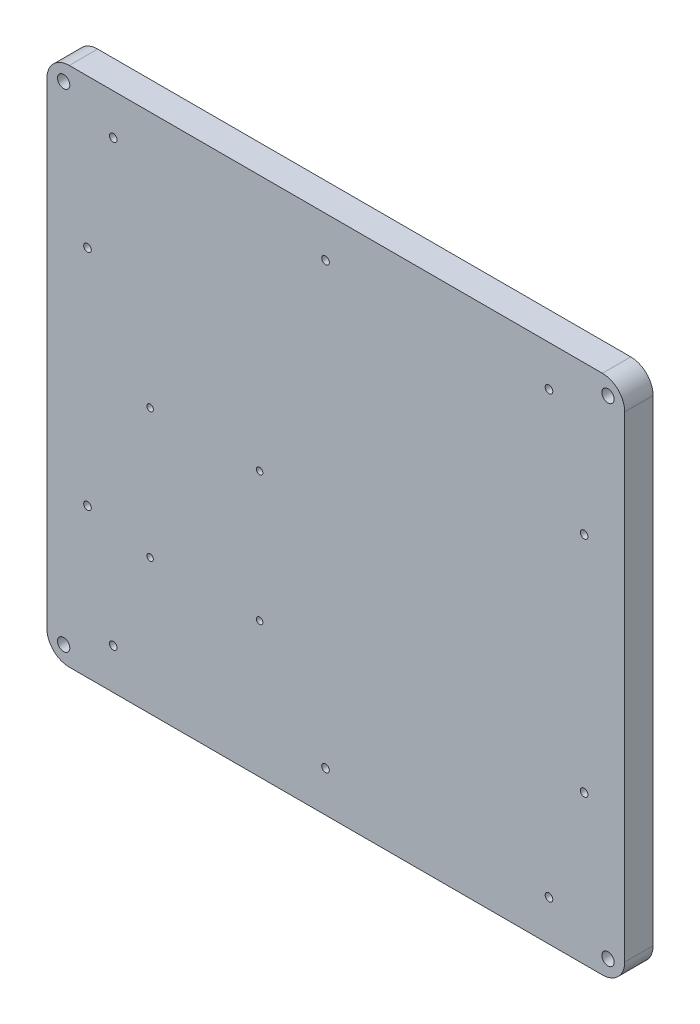
SolidWorks part; units mm, degrees
material "Aleación 6061"
ref_plane "Alzado" through (0, 0, 0) normal (0, 0, 1) x (1, 0, 0)
ref_plane "Planta" through (0, 0, 0) normal (0, 1, 0) x (1, 0, 0)
ref_plane "Vista lateral" through (0, 0, 0) normal (1, 0, 0) x (0, 0, -1)
ref_axis "Eje_J1" through (0, 0, -0.635) along (0, 0, 1)
sketch "Croquis19" plane through (0, 0, 0) normal (0, 0, 1) x (1, 0, 0)
  line L0 (-144.7, -116.6) -> (93.9, -116.6)
  line L1 (103.9, -106.6) -> (103.9, 106.6)
  line L2 (93.9, 116.6) -> (-144.7, 116.6)
  line L3 (-154.7, 106.6) -> (-154.7, -106.6)
  arc A0 (93.9, -116.6) -> (103.9, -106.6) centre (93.9, -106.6) ccw
  arc A1 (103.9, 106.6) -> (93.9, 116.6) centre (93.9, 106.6) ccw
  arc A2 (-144.7, 116.6) -> (-154.7, 106.6) centre (-144.7, 106.6) ccw
  arc A3 (-154.7, -106.6) -> (-144.7, -116.6) centre (-144.7, -106.6) ccw
  dimension "D1" = 10
  dimension "D2" = 10
  dimension "D3" = 10
  dimension "D4" = 10
  dimension "D5" = 144.7
  dimension "D6" = 116.6
  dimension "D7" = 93.9
  dimension "D8" = 116.6
  dimension "D9" = 103.9
  dimension "D10" = 106.6
  dimension "D11" = 103.9
  dimension "D12" = 106.6
  dimension "D13" = 93.9
  dimension "D14" = 116.6
  dimension "D15" = 144.7
  dimension "D16" = 116.6
  dimension "D17" = 154.7
  dimension "D18" = 106.6
  dimension "D19" = 154.7
  dimension "D20" = 106.6
extrude "Placa_inferior_1-2in" add sketch "Croquis19" along normal blind 12.7
sketch "Croquis20" plane through (0, 0, 0) normal (0, 0, 1) x (1, 0, 0)
  circle A0 centre (-147.2, -109.1) radius 2.75
  circle A1 centre (-147.2, 109.1) radius 2.75
  circle A2 centre (96.4, -109.1) radius 2.75
  circle A3 centre (96.4, 109.1) radius 2.75
  dimension "D1" = 5.5
  dimension "D2" = 5.5
  dimension "D3" = 5.5
  dimension "D4" = 5.5
  dimension "D5" = 147.2
  dimension "D6" = 109.1
  dimension "D7" = 147.2
  dimension "D8" = 109.1
  dimension "D9" = 96.4
  dimension "D10" = 109.1
  dimension "D11" = 96.4
  dimension "D12" = 109.1
extrude "Anclajes_4xM5" cut sketch "Croquis20" along normal blind 12.7
sketch "Croquis21" plane through (0, 0, 0) normal (0, 0, 1) x (1, 0, 0)
  circle A0 centre (-125, 98.425) radius 1.7
  circle A1 centre (-125, -98.425) radius 1.7
  circle A2 centre (-30, 98.425) radius 1.7
  circle A3 centre (-30, -98.425) radius 1.7
  circle A4 centre (70, 98.425) radius 1.7
  circle A5 centre (70, -98.425) radius 1.7
  circle A6 centre (-136.525, -50) radius 1.7
  circle A7 centre (-136.525, 50) radius 1.7
  circle A8 centre (85.725, -50) radius 1.7
  circle A9 centre (85.725, 50) radius 1.7
  circle A10 centre (-108.5, -56) radius 1.45
  circle A11 centre (-108.5, 2) radius 1.45
  circle A12 centre (-59.5, -56) radius 1.45
  circle A13 centre (-59.5, 2) radius 1.45
  dimension "D1" = 3.4
  dimension "D2" = 3.4
  dimension "D3" = 3.4
  dimension "D4" = 3.4
  dimension "D5" = 3.4
  dimension "D6" = 3.4
  dimension "D7" = 3.4
  dimension "D8" = 3.4
  dimension "D9" = 3.4
  dimension "D10" = 3.4
  dimension "D11" = 2.9
  dimension "D12" = 2.9
  dimension "D13" = 2.9
  dimension "D14" = 2.9
  dimension "D15" = 125
  dimension "D16" = 98.425
  dimension "D17" = 125
  dimension "D18" = 98.425
  dimension "D19" = 30
  dimension "D20" = 98.425
  dimension "D21" = 30
  dimension "D22" = 98.425
  dimension "D23" = 70
  dimension "D24" = 98.425
  dimension "D25" = 70
  dimension "D26" = 98.425
  dimension "D27" = 136.525
  dimension "D28" = 50
  dimension "D29" = 136.525
  dimension "D30" = 50
  dimension "D31" = 85.725
  dimension "D32" = 50
  dimension "D33" = 85.725
  dimension "D34" = 50
  dimension "D35" = 108.5
  dimension "D36" = 56
  dimension "D37" = 108.5
  dimension "D38" = 2
  dimension "D39" = 59.5
  dimension "D40" = 56
  dimension "D41" = 59.5
  dimension "D42" = 2
extrude "Barrenos_M3_paredes_y_M2-5_postes" cut sketch "Croquis21" along normal blind 12.7
sketch "Croquis22" plane through (0, 0, 0) normal (0, 0, 1) x (1, 0, 0)
  circle A0 centre (-125, 98.425) radius 2.9
  circle A1 centre (-125, -98.425) radius 2.9
  circle A2 centre (-30, 98.425) radius 2.9
  circle A3 centre (-30, -98.425) radius 2.9
  circle A4 centre (70, 98.425) radius 2.9
  circle A5 centre (70, -98.425) radius 2.9
  circle A6 centre (-136.525, -50) radius 2.9
  circle A7 centre (-136.525, 50) radius 2.9
  circle A8 centre (85.725, -50) radius 2.9
  circle A9 centre (85.725, 50) radius 2.9
  dimension "D1" = 5.8
  dimension "D2" = 5.8
  dimension "D3" = 5.8
  dimension "D4" = 5.8
  dimension "D5" = 5.8
  dimension "D6" = 5.8
  dimension "D7" = 5.8
  dimension "D8" = 5.8
  dimension "D9" = 5.8
  dimension "D10" = 5.8
  dimension "D11" = 125
  dimension "D12" = 98.425
  dimension "D13" = 125
  dimension "D14" = 98.425
  dimension "D15" = 30
  dimension "D16" = 98.425
  dimension "D17" = 30
  dimension "D18" = 98.425
  dimension "D19" = 70
  dimension "D20" = 98.425
  dimension "D21" = 70
  dimension "D22" = 98.425
  dimension "D23" = 136.525
  dimension "D24" = 50
  dimension "D25" = 136.525
  dimension "D26" = 50
  dimension "D27" = 85.725
  dimension "D28" = 50
  dimension "D29" = 85.725
  dimension "D30" = 50
extrude "Refrentado_M3_inferior" cut sketch "Croquis22" along normal blind 3.2
sketch "Croquis23" plane through (0, 0, 0) normal (0, 0, 1) x (1, 0, 0)
  circle A0 centre (-108.5, -56) radius 2.5
  circle A1 centre (-108.5, 2) radius 2.5
  circle A2 centre (-59.5, -56) radius 2.5
  circle A3 centre (-59.5, 2) radius 2.5
  dimension "D1" = 5
  dimension "D2" = 5
  dimension "D3" = 5
  dimension "D4" = 5
  dimension "D5" = 108.5
  dimension "D6" = 56
  dimension "D7" = 108.5
  dimension "D8" = 2
  dimension "D9" = 59.5
  dimension "D10" = 56
  dimension "D11" = 59.5
  dimension "D12" = 2
extrude "Refrentado_M2-5_inferior" cut sketch "Croquis23" along normal blind 2.6
